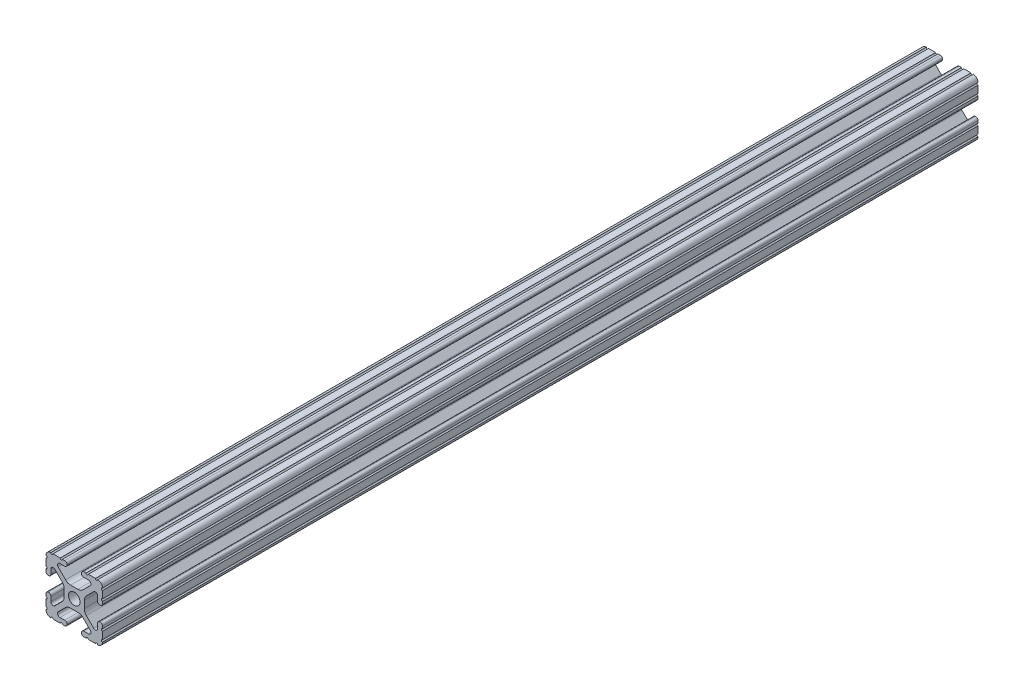
SolidWorks part; units mm, degrees
material "6105-T5 Aluminum"
ref_plane "Front Plane" through (0, 0, 0) normal (0, 0, 1) x (1, 0, 0)
ref_plane "Top Plane" through (0, 0, 0) normal (0, 1, 0) x (1, 0, 0)
ref_plane "Right Plane" through (0, 0, 0) normal (1, 0, 0) x (0, 0, -1)
sketch "Sketch1" plane through (0, 0, 0) normal (0, 0, 1) x (1, 0, 0)
  line L0 (-7.207, 8.7244) -> (-3.8983, 5.4232)
  line L1 (-4.2875, 10.4902) -> (-6.4768, 10.4902)
  line L2 (-3.2385, 11.651) -> (-3.2385, 11.5392)
  line L3 (-5.3171, 12.7) -> (-4.2875, 12.7)
  line L4 (0, 13.4005) -> (0, -14.8534) construction
  line L5 (12.7, 0) -> (-13.9989, 0) construction
  line L6 (-9.5504, 12.7) -> (-6.3331, 12.7)
  line L7 (-12.7, 6.3331) -> (-12.7, 9.5504)
  line L8 (-12.7, 4.2875) -> (-12.7, 5.3171)
  line L9 (-11.5392, 3.2385) -> (-11.651, 3.2385)
  line L10 (-10.4902, 6.4021) -> (-10.4902, 4.2875)
  line L11 (-5.441, 3.8408) -> (-8.7371, 7.1294)
  line L12 (-4.5085, -1.5932) -> (-4.5085, 1.5932)
  line L13 (-1.7093, -4.4958) -> (1.7093, -4.4958)
  line L14 (3.9523, -5.4237) -> (7.1797, -8.6452)
  line L15 (6.4164, -10.4902) -> (4.2875, -10.4902)
  line L16 (3.2385, -11.5392) -> (3.2385, -11.651)
  line L17 (4.2875, -12.7) -> (5.3171, -12.7)
  line L18 (6.3331, -12.7) -> (9.5504, -12.7)
  line L19 (12.7, -9.5504) -> (12.7, -6.3331)
  line L20 (12.7, -5.3171) -> (12.7, -4.2875)
  line L21 (11.651, -3.2385) -> (11.5392, -3.2385)
  line L22 (10.4902, -4.2875) -> (10.4902, -6.4021)
  line L23 (8.7371, -7.1294) -> (5.441, -3.8408)
  line L24 (4.5085, -1.5932) -> (4.5085, 1.5932)
  line L25 (5.441, 3.8408) -> (8.7371, 7.1294)
  line L26 (10.4902, 6.4021) -> (10.4902, 4.2875)
  line L27 (11.5392, 3.2385) -> (11.651, 3.2385)
  line L28 (12.7, 4.2875) -> (12.7, 5.3171)
  line L29 (12.7, 6.3331) -> (12.7, 9.5504)
  line L30 (9.5504, 12.7) -> (6.3331, 12.7)
  line L31 (5.3171, 12.7) -> (4.2875, 12.7)
  line L32 (3.2385, 11.651) -> (3.2385, 11.5392)
  line L33 (4.2875, 10.4902) -> (6.4768, 10.4902)
  line L34 (7.207, 8.7244) -> (3.8983, 5.4232)
  line L35 (1.6558, 4.4958) -> (-1.6558, 4.4958)
  line L36 (-8.7371, -7.1294) -> (-5.441, -3.8408)
  line L37 (-10.4902, -4.2875) -> (-10.4902, -6.4021)
  line L38 (-11.651, -3.2385) -> (-11.5392, -3.2385)
  line L39 (-12.7, -5.3171) -> (-12.7, -4.2875)
  line L40 (-12.7, -9.5504) -> (-12.7, -6.3331)
  line L41 (-6.3331, -12.7) -> (-9.5504, -12.7)
  line L42 (-4.2875, -12.7) -> (-5.3171, -12.7)
  line L43 (-3.2385, -11.5392) -> (-3.2385, -11.651)
  line L44 (-6.4164, -10.4902) -> (-4.2875, -10.4902)
  line L45 (-3.9523, -5.4237) -> (-7.1797, -8.6452)
  arc A0 (-7.207, 8.7244) -> (-6.4768, 10.4902) centre (-6.4768, 9.4563) cw
  arc A1 (-3.2385, 11.5392) -> (-4.2875, 10.4902) centre (-4.2875, 11.5392) cw
  arc A2 (-4.2875, 12.7) -> (-3.2385, 11.651) centre (-4.2875, 11.651) cw
  arc A3 (-5.3171, 12.7) -> (-6.3331, 12.7) centre (-5.8251, 12.7) cw
  arc A4 (-9.5504, 12.7) -> (-10.5664, 12.6998) centre (-10.0584, 12.7) cw
  arc A5 (-12.6998, 10.5664) -> (-10.5664, 12.6998) centre (-10.5918, 10.5918) cw
  arc A6 (-12.6998, 10.5664) -> (-12.7, 9.5504) centre (-12.7, 10.0584) cw
  arc A7 (-12.7, 6.3331) -> (-12.7, 5.3171) centre (-12.7, 5.8251) cw
  arc A8 (-11.651, 3.2385) -> (-12.7, 4.2875) centre (-11.651, 4.2875) cw
  arc A9 (-10.4902, 4.2875) -> (-11.5392, 3.2385) centre (-11.5392, 4.2875) cw
  circle A10 centre (0, 0) radius 2.6035
  arc A11 (-10.4902, 6.4021) -> (-8.7371, 7.1294) centre (-9.4628, 6.4021) cw
  arc A12 (-5.441, 3.8408) -> (-4.5085, 1.5932) centre (-7.6835, 1.5932) cw
  arc A13 (-4.5085, -1.5932) -> (-5.441, -3.8408) centre (-7.6835, -1.5932) cw
  arc A14 (-8.7371, -7.1294) -> (-10.4902, -6.4021) centre (-9.4628, -6.4021) cw
  arc A15 (-1.7093, -4.4958) -> (-3.9523, -5.4237) centre (-1.7093, -7.6708) ccw
  arc A16 (3.9523, -5.4237) -> (1.7093, -4.4958) centre (1.7093, -7.6708) ccw
  arc A17 (6.4164, -10.4902) -> (7.1797, -8.6452) centre (6.4164, -9.4098) ccw
  arc A18 (4.2875, -10.4902) -> (3.2385, -11.5392) centre (4.2875, -11.5392) ccw
  arc A19 (3.2385, -11.651) -> (4.2875, -12.7) centre (4.2875, -11.651) ccw
  arc A20 (6.3331, -12.7) -> (5.3171, -12.7) centre (5.8251, -12.7) ccw
  arc A21 (10.5664, -12.6998) -> (9.5504, -12.7) centre (10.0584, -12.7) ccw
  arc A22 (10.5664, -12.6998) -> (12.6998, -10.5664) centre (10.5918, -10.5918) ccw
  arc A23 (12.7, -9.5504) -> (12.6998, -10.5664) centre (12.7, -10.0584) ccw
  arc A24 (12.7, -5.3171) -> (12.7, -6.3331) centre (12.7, -5.8251) ccw
  arc A25 (12.7, -4.2875) -> (11.651, -3.2385) centre (11.651, -4.2875) ccw
  arc A26 (11.5392, -3.2385) -> (10.4902, -4.2875) centre (11.5392, -4.2875) ccw
  arc A27 (8.7371, -7.1294) -> (10.4902, -6.4021) centre (9.4628, -6.4021) ccw
  arc A28 (4.5085, -1.5932) -> (5.441, -3.8408) centre (7.6835, -1.5932) ccw
  arc A29 (5.441, 3.8408) -> (4.5085, 1.5932) centre (7.6835, 1.5932) ccw
  arc A30 (10.4902, 6.4021) -> (8.7371, 7.1294) centre (9.4628, 6.4021) ccw
  arc A31 (10.4902, 4.2875) -> (11.5392, 3.2385) centre (11.5392, 4.2875) ccw
  arc A32 (11.651, 3.2385) -> (12.7, 4.2875) centre (11.651, 4.2875) ccw
  arc A33 (12.7, 6.3331) -> (12.7, 5.3171) centre (12.7, 5.8251) ccw
  arc A34 (12.6998, 10.5664) -> (12.7, 9.5504) centre (12.7, 10.0584) ccw
  arc A35 (12.6998, 10.5664) -> (10.5664, 12.6998) centre (10.5918, 10.5918) ccw
  arc A36 (9.5504, 12.7) -> (10.5664, 12.6998) centre (10.0584, 12.7) ccw
  arc A37 (5.3171, 12.7) -> (6.3331, 12.7) centre (5.8251, 12.7) ccw
  arc A38 (4.2875, 12.7) -> (3.2385, 11.651) centre (4.2875, 11.651) ccw
  arc A39 (3.2385, 11.5392) -> (4.2875, 10.4902) centre (4.2875, 11.5392) ccw
  arc A40 (7.207, 8.7244) -> (6.4768, 10.4902) centre (6.4768, 9.4563) ccw
  arc A41 (1.6558, 4.4958) -> (3.8983, 5.4232) centre (1.6558, 7.6708) ccw
  arc A42 (-1.6558, 4.4958) -> (-3.8983, 5.4232) centre (-1.6558, 7.6708) cw
  arc A43 (-11.5392, -3.2385) -> (-10.4902, -4.2875) centre (-11.5392, -4.2875) cw
  arc A44 (-12.7, -4.2875) -> (-11.651, -3.2385) centre (-11.651, -4.2875) cw
  arc A45 (-12.7, -5.3171) -> (-12.7, -6.3331) centre (-12.7, -5.8251) cw
  arc A46 (-12.7, -9.5504) -> (-12.6998, -10.5664) centre (-12.7, -10.0584) cw
  arc A47 (-10.5664, -12.6998) -> (-12.6998, -10.5664) centre (-10.5918, -10.5918) cw
  arc A48 (-10.5664, -12.6998) -> (-9.5504, -12.7) centre (-10.0584, -12.7) cw
  arc A49 (-6.3331, -12.7) -> (-5.3171, -12.7) centre (-5.8251, -12.7) cw
  arc A50 (-3.2385, -11.651) -> (-4.2875, -12.7) centre (-4.2875, -11.651) cw
  arc A51 (-4.2875, -10.4902) -> (-3.2385, -11.5392) centre (-4.2875, -11.5392) cw
  arc A52 (-6.4164, -10.4902) -> (-7.1797, -8.6452) centre (-6.4164, -9.4098) cw
  dimension "D1" = 5.207
  dimension "D9" = 14.859
  dimension "D2" = 25.4
  dimension "D3" = 12.7
  dimension "D4" = 6.477
  dimension "D5" = 8.2042
  dimension "D6" = 9.017
  dimension "D8" = 2.2098
  dimension "D10" = 2.2098
extrude "Extrude1" add sketch "Sketch1" against normal blind 393.7
